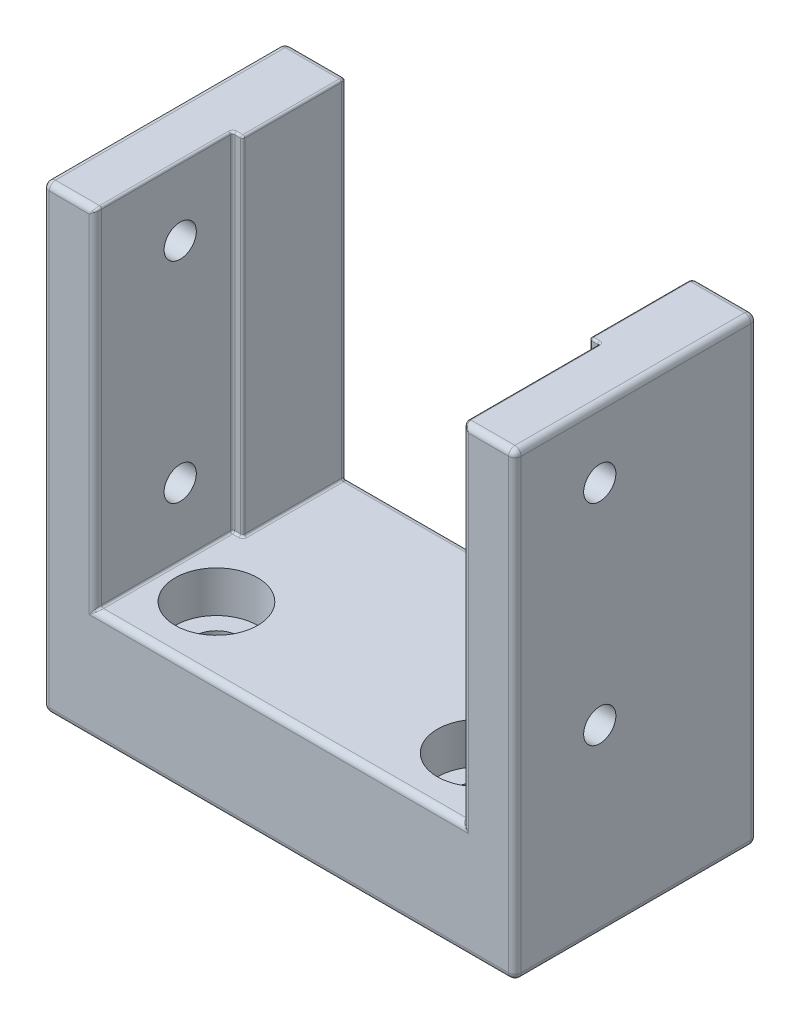
SolidWorks part; units mm, degrees
material "ABS"
ref_plane "Front Plane" through (0, 0, 0) normal (0, 0, 1) x (1, 0, 0)
ref_plane "Top Plane" through (0, 0, 0) normal (0, 1, 0) x (1, 0, 0)
ref_plane "Right Plane" through (0, 0, 0) normal (1, 0, 0) x (0, 0, -1)
sketch "Sketch1" plane through (0, 0, 0) normal (0, 1, 0) x (1, 0, 0)
  line L1 (-22.225, 14.6625) -> (22.225, 14.6625)
  line L2 (-22.225, 14.6625) -> (-22.225, -14.6625)
  line L3 (-22.225, -14.6625) -> (22.225, -14.6625)
  line L4 (22.225, 14.6625) -> (22.225, -14.6625)
  point P4 (0, -14.6625)
  point P6 (-22.225, 0)
  dimension "D1" = 29.325
  dimension "D2" = 44.45
extrude "Boss-Extrude1" add sketch "Sketch1" against normal blind 13.685
sketch "Sketch2" plane through (22.225, 0, 0) normal (1, 0, 0) x (0, 0, -1)
  line L0 (14.6625, -13.685) -> (14.6625, 0) construction
  line L1 (-14.6625, -13.685) -> (14.6625, -13.685)
  line L2 (-14.6625, -13.685) -> (-14.6625, 42)
  line L3 (-14.6625, 42) -> (14.6625, 42)
  line L4 (14.6625, -13.685) -> (14.6625, 42)
  point P5 (53.9626, -43.6182)
  point P6 (53.6601, -69.0155)
  dimension "D1" = 55.685
extrude "Boss-Extrude2" add sketch "Sketch2" along normal blind 6.35
hole_wizard "M3.5 Clearance Hole1" positions "Sketch5" profile "Sketch6" hole size "M3.5" standard "ANSI Metric" end condition through all
sketch "Sketch5" plane through (28.575, 0, 0) normal (1, 0, 0) x (0, 0, -1)
  line L1 (14.6625, 42) -> (-14.6625, 42) construction
  line L2 (-14.6625, 42) -> (-14.6625, -13.685) construction
  point P0 (-4.3875, 33.7)
  point P2 (-4.3875, 8.3)
  dimension "D1" = 10.275
  dimension "D2" = 8.3
  dimension "D3" = 25.4
sketch "Sketch6" plane through (28.575, 33.7, 4.3875) normal (0, 1, 0) x (0, 0, -1)
  line L0 (0, 0) -> (0, 50.8)
  line L1 (0, 50.8) -> (1.95, 50.8)
  line L2 (1.95, 50.8) -> (1.95, 0)
  line L5 (1.95, 0) -> (0, 0)
  line L11 (0, -6.35) -> (0, 107.95) construction
  dimension "Thru Hole Dia." = 3.9
  dimension "Thru Hole Depth" = 50.8
mirror "Mirror1" about plane through (0, 0, 0) normal (1, 0, 0) of "Boss-Extrude2", "M3.5 Clearance Hole1"
sketch "Sketch8" plane through (22.225, 0, 0) normal (-1, 0, 0) x (0, 0, 1)
  line L0 (-14.6625, 42) -> (14.6625, 42) construction
  line L1 (-14.6625, 0) -> (-1.9625, 0)
  line L2 (-14.6625, 0) -> (-14.6625, 42)
  line L3 (-14.6625, 42) -> (-1.9625, 42)
  line L4 (-1.9625, 0) -> (-1.9625, 42)
  dimension "D1" = 12.7
extrude "Boss-Extrude6" add sketch "Sketch8" along normal blind 1.225
mirror "Mirror2" about plane through (0, 0, 0) normal (1, 0, 0) of "Boss-Extrude6"
hole_wizard "CBORE for M5 SHCS1" positions "Sketch9" profile "Sketch10" counterbore size "M5" standard "ANSI Metric" end condition through all
sketch "Sketch9" plane through (0, 0, 0) normal (0, 1, 0) x (1, 0, 0)
  line L0 (-22.225, 1.9625) -> (-22.225, -14.6625) construction
  line L1 (0, -16.1288) -> (0, 16.1288) construction
  point P0 (15.875, -6.35)
  point P2 (-15.875, -6.35)
  point P8 (-22.225, -6.35)
  dimension "D1" = 15.875
  dimension "D2" = 15.875
sketch "Sketch10" plane through (15.875, 0, 6.35) normal (1, 0, 0) x (0, 0, 1)
  line L0 (0, 0) -> (0, 13.685)
  line L1 (0, 13.685) -> (2.75, 13.685)
  line L3 (2.75, 13.685) -> (2.75, 5)
  line L4 (2.75, 5) -> (5, 5)
  line L5 (5, 5) -> (5, 0)
  line L7 (5, 0) -> (0, 0)
  line L11 (0, -6.35) -> (0, 107.95) construction
  dimension "Thru Hole Dia." = 5.5
  dimension "Thru Hole Depth" = 13.685
  dimension "C'Bore Dia." = 10
  dimension "C'Bore Depth" = 5
fillet "Fillet1" radius 0.762 22 edges at (-21, 21, -14.6625) (-24.7875, 42, -14.6625) (-28.575, 14.1575, -14.6625) (28.575, 14.1575, -14.6625) (24.7875, 42, -14.6625) (21, 21, -14.6625) (0, 0, -14.6625) (22.225, 21, 14.6625) (25.4, 42, 14.6625) (28.575, 14.1575, 14.6625) (-28.575, 14.1575, 14.6625) (-25.4, 42, 14.6625) (-22.225, 21, 14.6625) (0, 0, 14.6625) (28.575, -13.685, 0) (0, -13.685, -14.6625) (-28.575, -13.685, 0) (0, -13.685, 14.6625) (-15.875, -13.685, 9.1) (15.875, -13.685, 9.1) (28.575, 42, 0) (-28.575, 42, 0)
fillet "Fillet2" radius 0.254 24 edges at (-21.2232, -0.2232, -14.4393) (21.2232, -0.2232, -14.4393) (22.4482, 41.7768, 14.4393) (-21, 0, -7.9315) (21, 0, -7.9315) (22.225, 42, 5.969) (-22.4482, -0.2232, 14.4393) (-21.2232, 41.7768, -14.4393) (-22.4482, 41.7768, 14.4393) (22.4482, -0.2232, 14.4393) (21.2232, 41.7768, -14.4393) (-22.225, 0, 5.969) (-21.6125, 0, -1.9625) (-21, 42, -7.9315) (-21, 21, -1.9625) (-22.225, 21, -1.9625) (-21.6125, 42, -1.9625) (-22.225, 42, 5.969) (21.6125, 0, -1.9625) (22.225, 0, 5.969) (21.6125, 42, -1.9625) (21, 21, -1.9625) (22.225, 21, -1.9625) (21, 42, -7.9315)
sketch "Sketch11" plane through (0, -13.685, 0) normal (0, -1, 0) x (1, 0, 0)
  line L0 (-15.875, 6.35) -> (15.875, 6.35) construction
  line L1 (15.875, 6.35) -> (27.813, 6.35) construction
  line L2 (27.813, -13.9005) -> (27.813, 13.9005) construction
  line L3 (27.813, 6.35) -> (-27.813, 6.35) construction
  line L4 (-27.813, 13.9005) -> (-27.813, -13.9005) construction
  line L5 (0, 6.35) -> (0, 0) construction
  circle A0 centre (0, 6.35) radius 6.35
